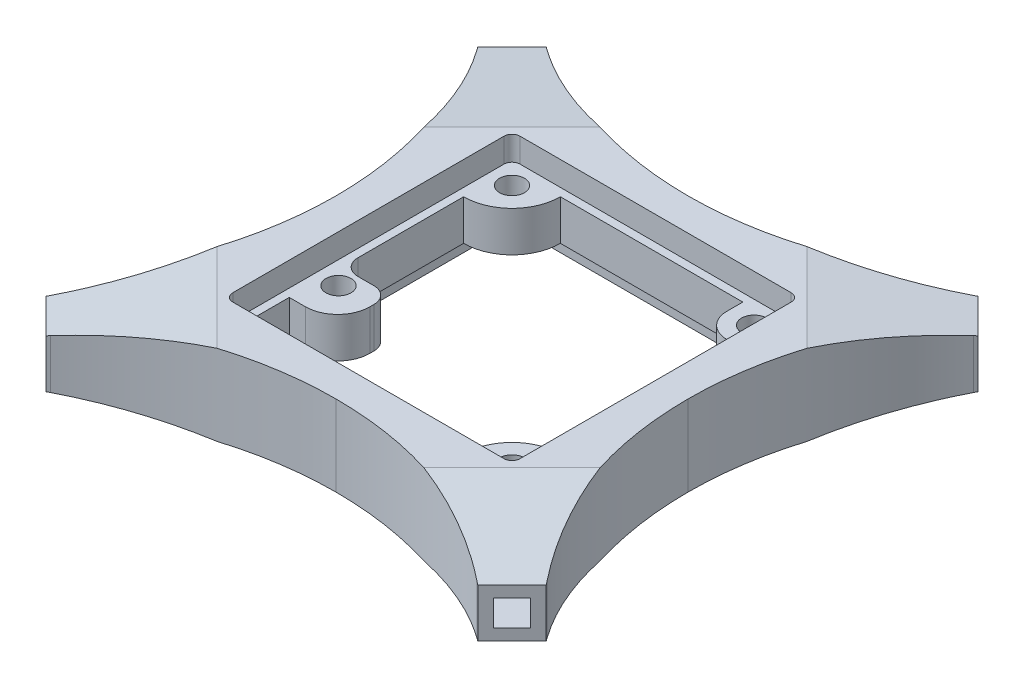
SolidWorks part; units mm, degrees
ref_plane "Plan de face" through (0, 0, 0) normal (0, 0, 1) x (1, 0, 0)
ref_plane "Plan de dessus" through (0, 0, 0) normal (0, 1, 0) x (1, 0, 0)
ref_plane "Plan de droite" through (0, 0, 0) normal (1, 0, 0) x (0, 0, -1)
sketch "Esquisse1" plane through (0, 0, 0) normal (0, 1, 0) x (1, 0, 0)
  line L0 (21.8, -14.7289) -> (32.4066, -25.3355)
  line L1 (-17.8, -17.8) -> (17.8, -17.8)
  line L2 (-17.8, -17.8) -> (-17.8, 17.8)
  line L3 (-17.8, 17.8) -> (17.8, 17.8)
  line L4 (17.8, -17.8) -> (17.8, 17.8)
  line L5 (-17.8, -17.8) -> (17.8, 17.8) construction
  line L6 (-17.8, 17.8) -> (17.8, -17.8) construction
  line L7 (-21.8, -21.8) -> (21.8, -21.8)
  line L8 (-21.8, -21.8) -> (-21.8, 21.8)
  line L9 (-21.8, 21.8) -> (21.8, 21.8)
  line L10 (21.8, -21.8) -> (21.8, 21.8)
  line L11 (-21.8, -21.8) -> (21.8, 21.8) construction
  line L12 (-21.8, 21.8) -> (21.8, -21.8) construction
  line L13 (32.4066, -25.3355) -> (25.3355, -32.4066)
  line L14 (25.3355, -32.4066) -> (14.7289, -21.8)
  line L15 (14.7289, -21.8) -> (21.8, -14.7289) construction
  line L16 (-14.7289, -21.8) -> (-25.3355, -32.4066)
  line L17 (-25.3355, -32.4066) -> (-32.4066, -25.3355)
  line L18 (-32.4066, -25.3355) -> (-21.8, -14.7289)
  line L19 (-21.8, 14.7289) -> (-32.4066, 25.3355)
  line L20 (-32.4066, 25.3355) -> (-25.3355, 32.4066)
  line L21 (-25.3355, 32.4066) -> (-14.7289, 21.8)
  line L22 (14.7289, 21.8) -> (25.3355, 32.4066)
  line L23 (25.3355, 32.4066) -> (32.4066, 25.3355)
  line L24 (32.4066, 25.3355) -> (21.8, 14.7289)
  point P0 (0, 0)
  point P7 (0, 0)
  point P30 (0, 0)
  dimension "D2" = 35.6
  dimension "D3" = 4
  dimension "D4" = 10
  dimension "D5" = 15
  dimension "D6" = 4
extrude "Boss.-Extru.1" add sketch "Esquisse1" along normal blind 10 contours L7 L10 L9 L8 L4 L1 L2 L3 | L14 L13 L0 L10 L7 | L24 L23 L22 L9 L10 | L21 L20 L19 L8 L9 | L18 L17 L16 L7 L8 region at (24.3927, 0, 24.3927) region at (21.1834, 0, 18.2645) region at (24.3927, 0, -24.3927) region at (-24.3927, 0, 24.3927) region at (-24.3927, 0, -24.3927)
sketch "Esquisse2" plane through (28.8711, 0, 28.8711) normal (0.7071, 0, 0.7071) x (0.7071, 0, -0.7071)
  line L0 (0, 0) -> (0, 10) construction
  line L1 (5, 10) -> (-5, 10) construction
  line L3 (-1.6, 3.4) -> (1.6, 3.4)
  line L4 (-1.6, 3.4) -> (-1.6, 6.6)
  line L5 (-1.6, 6.6) -> (1.6, 6.6)
  line L6 (1.6, 3.4) -> (1.6, 6.6)
  line L7 (-1.6, 3.4) -> (1.6, 6.6) construction
  line L8 (-1.6, 6.6) -> (1.6, 3.4) construction
  point P5 (0, 5)
  dimension "D1" = 3.2
extrude "Enlèv. mat.-Extru.1" cut sketch "Esquisse2" against normal blind 15
chamfer "Chanfrein1" distance 2 distance2 15 16 edges at (28.8711, 0, 28.8711) (25.3355, 5, 32.4066) (28.8711, 10, 28.8711) (32.4066, 5, 25.3355) (32.4066, 5, -25.3355) (28.8711, 10, -28.8711) (25.3355, 5, -32.4066) (28.8711, 0, -28.8711) (-25.3355, 5, -32.4066) (-28.8711, 10, -28.8711) (-32.4066, 5, -25.3355) (-28.8711, 0, -28.8711) (-32.4066, 5, 25.3355) (-28.8711, 10, 28.8711) (-25.3355, 5, 32.4066) (-28.8711, 0, 28.8711) first distance on face at (28.8711, 5, 28.8711) first distance on face at (28.8711, 5, -28.8711) first distance on face at (-28.8711, 5, -28.8711) first distance on face at (-28.8711, 5, 28.8711)
sketch "Esquisse3" plane through (0, 0, 0) normal (0, 0, 1) x (1, 0, 0)
  line L0 (0, 0) -> (0, 30) construction
  line L1 (-14.7289, 0) -> (14.7289, 0) construction
pattern_circular "Répétition circulaire10" count 4 every 90 about axis through (0, 0, 0) along (0, 1, 0) of "Enlèv. mat.-Extru.1"
sketch "Esquisse6" plane through (0, 0, 0) normal (0, -1, 0) x (1, 0, 0)
  line L0 (-17.8, 17.8) -> (-17.8, -17.8) construction
  line L1 (17.8, 17.8) -> (10.8, 17.8)
  line L2 (17.8, 17.8) -> (17.8, 10.8)
  line L3 (17.8, 10.8) -> (10.8, 10.8)
  line L4 (10.8, 17.8) -> (10.8, 10.8)
  line L5 (17.8, -17.8) -> (11.8, -17.8)
  line L6 (17.8, -17.8) -> (17.8, -11.8)
  line L7 (17.8, -11.8) -> (11.8, -11.8)
  line L8 (11.8, -17.8) -> (11.8, -11.8)
  line L9 (-17.8, -17.8) -> (-10.8, -17.8)
  line L10 (-17.8, -17.8) -> (-17.8, -10.8)
  line L11 (-17.8, -10.8) -> (-10.8, -10.8)
  line L12 (-10.8, -17.8) -> (-10.8, -10.8)
  line L13 (-17.8, 4.3) -> (-10.8, 4.3)
  line L14 (-17.8, 4.3) -> (-17.8, 10.8)
  line L15 (-17.8, 10.8) -> (-10.8, 10.8)
  line L16 (-10.8, 4.3) -> (-10.8, 10.8)
  line L17 (-17.8, 17.8) -> (17.8, 17.8) construction
  line L30 (16.8, 16.8) -> (-16.8, 16.8)
  line L31 (-16.8, -16.8) -> (16.8, -16.8)
  line L32 (-16.8, 16.8) -> (-16.8, -16.8)
  line L33 (16.8, -16.8) -> (16.8, 16.8)
  line L34 (16.8, 16.8) -> (-16.8, 16.8)
  line L35 (-16.8, -16.8) -> (16.8, -16.8)
  line L36 (-16.8, 16.8) -> (-16.8, -16.8)
  line L37 (16.8, -16.8) -> (16.8, 16.8)
  line L42 (-17.8, 17.8) -> (-17.8, -17.8)
  line L43 (17.8, 17.8) -> (-17.8, 17.8)
  line L44 (17.8, -17.8) -> (17.8, 17.8)
  line L45 (-17.8, -17.8) -> (17.8, -17.8)
  line L46 (-17.8, 17.8) -> (-17.8, -17.8)
  line L47 (17.8, 17.8) -> (-17.8, 17.8)
  line L48 (17.8, -17.8) -> (17.8, 17.8)
  line L49 (-17.8, -17.8) -> (17.8, -17.8)
  circle A4 centre (-15.0127, 6.4873) radius 1.55
  circle A5 centre (-15.0127, -15.0127) radius 1.55
  circle A6 centre (14.9874, -15.0127) radius 1.55
  circle A7 centre (14.9874, 14.9874) radius 1.55
  line M23 (17.8, 17.8) -> (17.8, -17.8)
  line M24 (17.8, -17.8) -> (-17.8, -17.8)
  line M25 (-17.8, -17.8) -> (-17.8, 17.8)
  line M26 (-17.8, 17.8) -> (17.8, 17.8)
  dimension "D10" = 3.1
  dimension "D1" = 7
  dimension "D2" = 7
  dimension "D3" = 6
  dimension "D4" = 6
  dimension "D5" = 7
  dimension "D6" = 7
  dimension "D7" = 7
  dimension "D8" = 13.5
  dimension "D9" = 7
  dimension "D11" = 1
  dimension "D12" = 0
extrude "Boss.-Extru.3" add sketch "Esquisse6" against normal blind 5 from offset 2 contours L15 L36 L13 L16 A4 | L11 L36 L35 L12 A5 | L35 L37 L7 L8 A6 | L37 L35 L8 L7 M24 M23 | L36 L11 L12 L35 M25 M24 | L36 L15 L13 M25 | L37 L3 L4 L34 M23 M26 | L37 L7 L3 M23 | L36 L34 L4 L15 M26 M25 | L36 L13 L11 M25 | L35 L12 L8 M24 | L3 L37 L34 L4 A7 | L14 L13 L16 L15 | L2 L1 L4 L3 | L6 L5 L8 L7 | L10 L9 L12 L11 | A7 | A6 | A4 | A5 region at (17.701, 0, 14.3) region at (10.5056, 0, 17.3) region at (17.3, 0, -0.5) region at (13.485, 0, 13.485) region at (17.7151, 0, -14.8) region at (-17.3, 0, 7.55) region at (16.7293, 0, -14.3) region at (-13.509, 0, 7.805) region at (-17.3, 0, -3.25) region at (0.5, 0, -17.3) region at (-17.3, 0, -10.899) region at (-13.4783, 0, -13.4783) offset against normal yes
fillet "Congé1" radius 6 2 edges at (-10.8, 4.5, -10.8) (10.8, 4.5, 10.8)
fillet "Congé2" radius 3 1 edges at (11.8, 4.5, -11.8)
fillet "Congé3" radius 4 1 edges at (-10.8, 4.5, 10.8)
fillet "Congé4" radius 2 1 edges at (-10.8, 4.5, 4.3)
fillet "Congé8" radius 1 8 edges at (-17.8, 8.5, 17.8) (-17.8, 1, 17.8) (17.8, 8.5, 17.8) (17.8, 8.5, -17.8) (-17.8, 8.5, -17.8) (-17.8, 1, -17.8) (17.8, 1, -17.8) (17.8, 1, 17.8)
fillet "Congé9" radius 43.5 8 edges at (-21.8, 5, 14.7289) (-21.8, 5, -14.7289) (-14.7289, 5, -21.8) (14.7289, 5, -21.8) (21.8, 5, -14.7289) (21.8, 5, 14.7289) (14.7289, 5, 21.8) (-14.7289, 5, 21.8)
fillet "Congé10" radius 2 1 edges at (-16.8, 4.5, 4.3)
